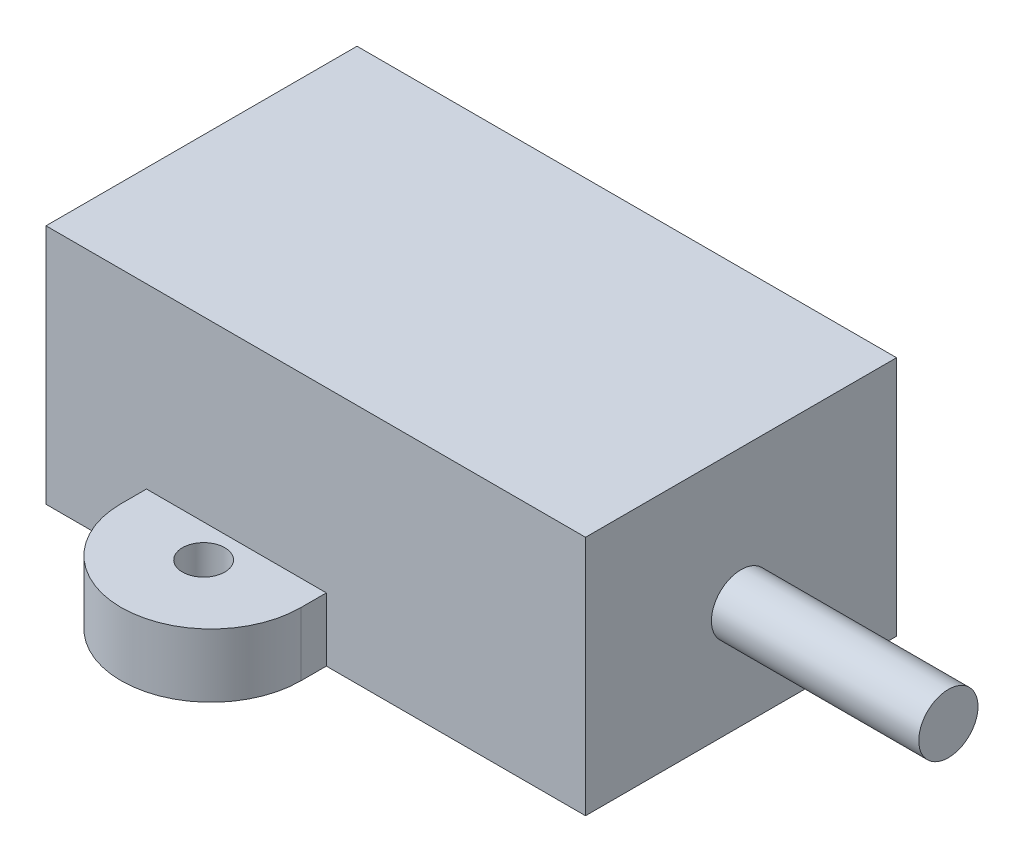
SolidWorks part; units mm, degrees
ref_plane "前视基准面" through (0, 0, 0) normal (0, 0, 1) x (1, 0, 0)
ref_plane "上视基准面" through (0, 0, 0) normal (0, 1, 0) x (1, 0, 0)
ref_plane "右视基准面" through (0, 0, 0) normal (1, 0, 0) x (0, 0, -1)
sketch "草图1" plane through (0, 0, 0) normal (0, 1, 0) x (1, 0, 0)
  line L1 (-12.75, 7.35) -> (12.75, 7.35)
  line L2 (-12.75, 7.35) -> (-12.75, -7.35)
  line L3 (-12.75, -7.35) -> (12.75, -7.35)
  line L4 (12.75, 7.35) -> (12.75, -7.35)
  line L5 (-12.75, 7.35) -> (12.75, -7.35) construction
  line L6 (-12.75, -7.35) -> (12.75, 7.35) construction
  point P0 (0, 0)
  dimension "D1" = 14.7
  dimension "D2" = 25.5
extrude "主体" add sketch "草图1" along normal blind 11.4
sketch "草图2" plane through (12.75, 0, 0) normal (1, 0, 0) x (0, 0, -1)
  line L0 (-7.35, 0) -> (7.35, 0) construction
  line L1 (0, 6.27) -> (0, -6.27) construction
  circle A0 centre (0, 5) radius 1.4
  dimension "D1" = 5
extrude "电机轴" add sketch "草图2" along normal blind 9.8
sketch "草图3" plane through (0, 0, 0) normal (0, -1, 0) x (1, 0, 0)
  line L0 (-3.75, -8.9) -> (-3.75, 8.9) construction
  line L1 (6.27, 0) -> (-6.27, 0) construction
  line L2 (12.75, 7.35) -> (12.75, -7.35) construction
  line L3 (-8, -7.35) -> (0.5, -7.35)
  line L4 (-8, -12.8) -> (0.5, -12.8)
  line L5 (-8, -12.8) -> (-8, 12.8) construction
  line L6 (-8, 12.8) -> (0.5, 12.8) construction
  line L7 (0.5, -12.8) -> (0.5, 12.8) construction
  line L8 (-8, -12.8) -> (0.5, 12.8) construction
  line L9 (-8, 12.8) -> (0.5, -12.8) construction
  line L10 (12.75, -7.35) -> (-12.75, -7.35) construction
  line L11 (-8, -12.8) -> (-8, -7.35)
  line L12 (0.5, -12.8) -> (0.5, -7.35)
  circle A0 centre (-3.75, -8.9) radius 1
  circle A1 centre (-3.75, 8.9) radius 1 construction
  point P3 (-3.75, 0)
  point P7 (-3.75, 0)
  point P16 (0, 0)
  dimension "D1" = 17.8
  dimension "D2" = 16.5
  dimension "D3" = 8.5
  dimension "D4" = 25.6
extrude "螺丝孔" add sketch "草图3" against normal blind 3
ref_axis "转轴" through (22.55, 5, 0) along (-1, 0, 0)
ref_plane "螺丝孔圆角切面" through (0, 0, -12.8) normal (0, 0, -1) x (-1, 0, 0)
fillet "圆角3" 2 edges at (-8, 1.5, -12.8) (0.5, 1.5, -12.8) type full round first side face at (-8, 1.5, -10.075) second side face at (0.5, 1.5, -10.075) middle face at (-3.75, 1.5, -12.8)
mirror "镜向3" about plane through (0, 0, 0) normal (0, 0, 1) of "圆角3", "螺丝孔"
